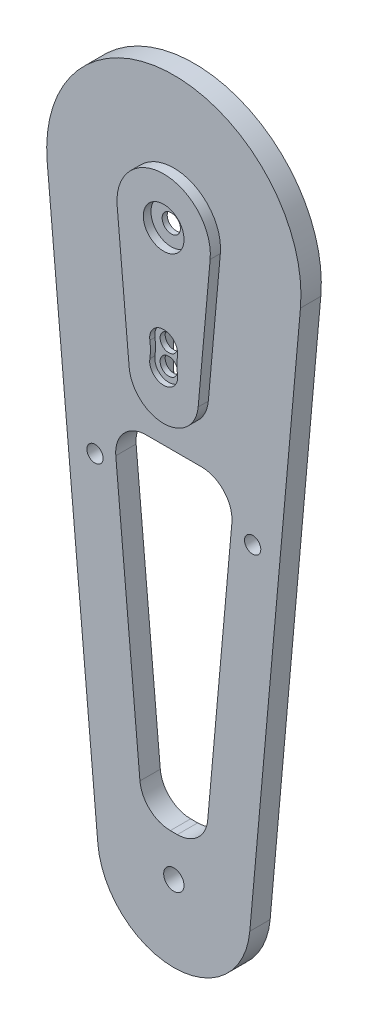
SolidWorks part; units mm, degrees
material "PLA"
ref_plane "Alzado" through (0, 0, 0) normal (0, 0, 1) x (1, 0, 0)
ref_plane "Planta" through (0, 0, 0) normal (0, 1, 0) x (1, 0, 0)
ref_plane "Vista lateral" through (0, 0, 0) normal (1, 0, 0) x (0, 0, -1)
other "PLA"
sketch "Croquis1" plane through (0, 0, 0) normal (0, 0, 1) x (1, 0, 0)
  line L0 (0, 112) -> (0, 0) construction
  line L1 (-14.9401, -1.3393) -> (-25.1002, 112)
  line L2 (14.9401, -1.3393) -> (24.9002, 109.7679)
  line L3 (0, 119.505) -> (19.4147, 119.505) construction
  line L4 (-3.55, 83.055) -> (-3.55, 100.9175)
  line L5 (3.55, 83.055) -> (3.55, 100.9175)
  line L11 (0, 112) -> (0, 123.4883) construction
  line L12 (0.5, 119.4883) -> (0.5, 119.505)
  arc A0 (-14.9401, -1.3393) -> (14.9401, -1.3393) centre (0, 0) ccw
  arc A1 (24.9002, 109.7679) -> (-24.9002, 109.7679) centre (0, 112) ccw
  circle A2 centre (0, 112) radius 7.505
  circle A3 centre (0, 0) radius 2
  circle A4 centre (0, 112) radius 1.65
  arc A5 (0, 79.505) -> (-3.55, 83.055) centre (0, 83.055) cw
  arc A6 (-5.8094, 107.2485) -> (-3.55, 100.9175) centre (-13.55, 100.9175) cw
  arc A7 (5.8094, 107.2485) -> (3.55, 100.9175) centre (13.55, 100.9175) ccw
  arc A8 (0, 79.505) -> (3.55, 83.055) centre (0, 83.055) ccw
  point P26 (0, 79.4404)
  dimension "D1" = 30
  dimension "D2" = 50
  dimension "D4" = 15.01
  dimension "D5" = 4
  dimension "D6" = 3.3
  dimension "D7" = 10
  dimension "D3" = 112
  dimension "D8" = 40
  dimension "D9" = 7.1
extrude "Saliente-Extruir1" add sketch "Croquis1" along normal blind 4 contours L2 A1 L1 A0 A2 A3 | A0 region at (0, 64.8855, 0)
ref_plane "Plano1" through (0, 0, 0) normal (1, 0, 0) x (0, -1, 0)
sketch "Croquis11" plane through (0, 0, 0) normal (0, 0, -1) x (-1, 0, 0)
  line L2 (0, 0) -> (0, 137) construction
  line L3 (-10.6804, 11.0037) -> (-15.5, 64.7681) construction
  line L4 (-14.9401, -1.3393) -> (-24.9002, 109.7679) construction
  arc A2 (24.9002, 109.7679) -> (-24.9002, 109.7679) centre (0, 112) ccw construction
  circle A3 centre (-15.5, 64.7681) radius 1.6
  circle A4 centre (15.5, 64.7681) radius 1.6
  dimension "D1" = 31
extrude "Cortar-Extruir1" cut sketch "Croquis11" against normal blind 6 contours A3 | A4
sketch "Croquis12" plane through (0, 0, 4) normal (0, 0, 1) x (1, 0, 0)
  line L0 (0, 79.5266) -> (0, 0) construction
  line L1 (-12, 73) -> (12, 73)
  line L2 (12, 73) -> (6.1732, 8)
  line L3 (6.1732, 8) -> (-6.1732, 8)
  line L4 (-12, 73) -> (-6.1732, 8)
  line L5 (14.9401, -1.3393) -> (24.9002, 109.7679) construction
  point P8 (0, 8)
  point P9 (0, 73)
  dimension "D1" = 24
  dimension "D2" = 65
  dimension "D3" = 8
extrude "Cortar-Extruir2" cut sketch "Croquis12" against normal up to next contours L4 | L0 L3 | L0 L3 | L2 | L1 L0 | L0 L1 region at (0, 43.9735, 4)
sketch "Croquis13" plane through (0, 0, 4) normal (0, 0, 1) x (1, 0, 0)
  line L0 (0, 137) -> (0, -15) construction
  line L2 (6.7847, 84.8645) -> (9.1438, 111.1803)
  line L3 (-6.7847, 84.8645) -> (-9.1438, 111.1803)
  line L4 (14.9401, -1.3393) -> (24.9002, 109.7679) construction
  arc A0 (-9.1438, 111.1803) -> (9.1438, 111.1803) centre (0, 112) ccw
  arc A2 (24.9002, 109.7679) -> (-24.9002, 109.7679) centre (0, 112) ccw construction
  arc A3 (-14.9401, -1.3393) -> (14.9401, -1.3393) centre (0, 0) ccw construction
  arc A4 (-9.1438, 111.1803) -> (9.1438, 111.1803) centre (0, 112) cw
  arc A5 (5.8094, 107.2485) -> (-5.8094, 107.2485) centre (0, 112) ccw construction
  arc A6 (6.7847, 84.8645) -> (-6.7847, 84.8645) centre (0, 85.4727) cw
  circle A7 centre (0, 112) radius 4
  circle A8 centre (0, 112) radius 1.8
  point P16 (0, 0)
  point P17 (0, 111.6502)
  dimension "D1" = 8
  dimension "D2" = 3.6
extrude "Saliente-Extruir2" add sketch "Croquis13" along normal blind 2 contours A6 L3 A4 L2 | A8
extrude "Saliente-Extruir3" add sketch "Croquis13<3>" against normal blind 0.5 contours L0 A7 | A7 | A8 region at (-3.8869, 112, 4)
sketch "Croquis13<3>" plane through (0, 0, 4) normal (0, 0, 1) x (1, 0, 0) same geometry as "Croquis13"
sketch "Croquis14" plane through (0, 0, 6) normal (0, 0, 1) x (1, 0, 0)
  circle A0 centre (0, 112) radius 4
  dimension "D1" = 8
extrude "Cortar-Extruir3" cut sketch "Croquis14" against normal blind 1.5
chamfer "Chaflán1" distance 0.5 angle 45 6 edges at (0, 79.505, 0) (-3.55, 91.9862, 0) (3.55, 91.9862, 0) (4.1318, 104.2785, 0) (-4.1318, 104.2785, 0) (0, 119.505, 0)
sketch "Croquis15" plane through (0, 0, 4) normal (0, 0, -1) x (-1, 0, 0)
  line L0 (0, 137) -> (0, -15) construction
  arc A0 (24.9002, 109.7679) -> (-24.9002, 109.7679) centre (0, 112) ccw construction
  arc A1 (-14.9401, -1.3393) -> (14.9401, -1.3393) centre (0, 0) ccw construction
  circle A2 centre (0, 87.915) radius 1.45
  circle A3 centre (0, 91.915) radius 1.45
  arc A4 (-3.55, 83.055) -> (3.55, 83.055) centre (0, 83.055) ccw construction
  circle A5 centre (0, 91.915) radius 0.75
  circle A6 centre (0, 87.915) radius 0.75
  point P15 (0, 79.505)
  dimension "D1" = 8.41
  dimension "D3" = 2.9
  dimension "D4" = 1.5
  dimension "D2" = 4
hole_wizard "Refrentado para tornillo con cabeza troncocónica de M31" positions "Croquis16" profile "Croquis17" counterbore size "M3" standard "Ansi Metric" end condition up to next
sketch "Croquis16" plane through (0, 0, 6) normal (0, 0, -1) x (-1, 0, 0)
  point P0 (0, 91.915)
  point P3 (0, 87.915)
sketch "Croquis17" plane through (0, 91.915, 6) normal (1, 0, 0) x (0, -1, 0)
  line L0 (0, 0) -> (0, 2)
  line L1 (0, 2) -> (1.7, 2)
  line L3 (1.7, 2) -> (1.7, 1)
  line L4 (1.7, 1) -> (2.75, 1)
  line L5 (2.75, 1) -> (2.75, 0)
  line L7 (2.75, 0) -> (0, 0)
  line L11 (0, -6.35) -> (0, 107.95) construction
  dimension "Diámetro de taladro hasta el siguiente" = 3.4
  dimension "Profundidad de taladro hasta el siguiente" = 2
  dimension "Diámetro de refrentado" = 5.5
  dimension "Profundidad de refrentado" = 1
fillet "Redondeo1" radius 10 2 edges at (-1.8875, 89.915, 5.5) (1.8875, 89.915, 5.5)
fillet "Redondeo2" radius 6 4 edges at (6.1732, 8, 2) (-6.1732, 8, 2) (12, 73, 2) (-12, 73, 2)
